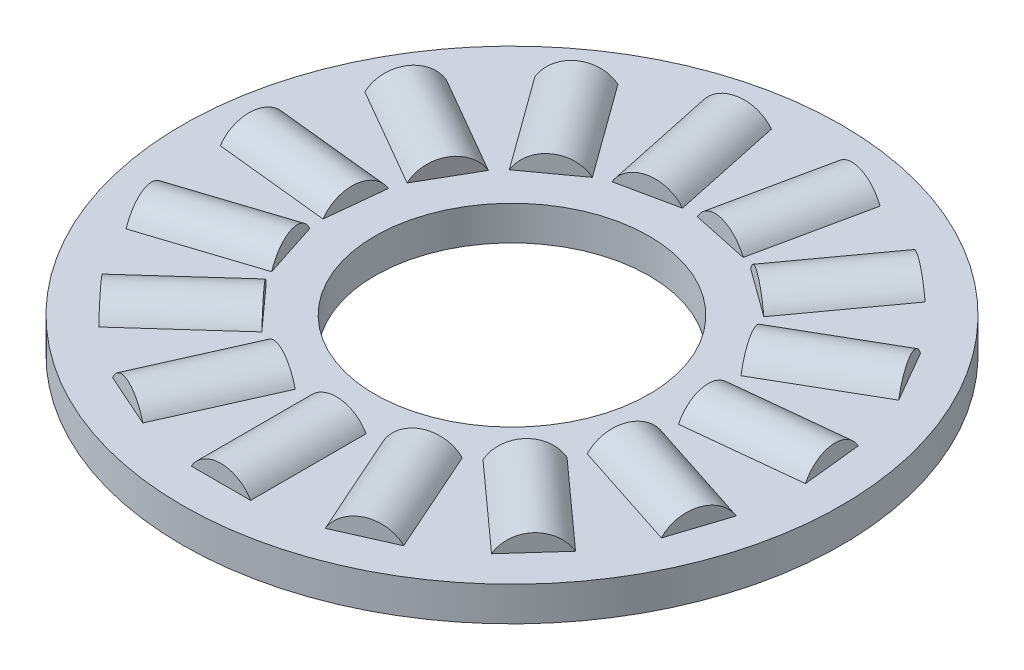
SolidWorks part; units mm, degrees
ref_plane "Front Plane" through (0, 0, 0) normal (0, 0, 1) x (1, 0, 0)
ref_plane "Top Plane" through (0, 0, 0) normal (0, 1, 0) x (1, 0, 0)
ref_plane "Right Plane" through (0, 0, 0) normal (1, 0, 0) x (0, 0, -1)
sketch "Sketch1" plane through (0, 0, 0) normal (1, 0, 0) x (0, 0, -1)
  line L0 (-9.525, 0) -> (9.525, 0) construction
  line L1 (0, -0.9922) -> (0, 0.9922) construction
  line L2 (-9.525, 0.4961) -> (-3.9624, 0.4961)
  line L3 (-9.525, 0.4961) -> (-9.525, -0.4961)
  line L4 (-9.525, -0.4961) -> (-3.9624, -0.4961)
  line L5 (-3.9624, 0.4961) -> (-3.9624, -0.4961)
  line L7 (-6.7437, 0.9922) -> (-6.7437, 0.4961) construction
  line L8 (-8.4125, 0.9922) -> (-5.0749, 0.9922) construction
  line L9 (-8.4125, 0.9922) -> (-8.4125, -0.9922) construction
  line L10 (-8.4125, -0.9922) -> (-5.0749, -0.9922) construction
  line L11 (-5.0749, 0.9922) -> (-5.0749, -0.9922) construction
  line L12 (9.525, 0.9922) -> (9.525, -0.9922) construction
  point P16 (-8.4125, 0)
  point P21 (9.525, 0)
  dimension "OD" = 19.05
  dimension "ID" = 7.9248
  dimension "Washer Thickness" = 0.9922
  dimension "D1" = 3.3376
  dimension "Thickness" = 1.9844
sketch "Sketch6" plane through (0, 0, 0) normal (0, 1, 0) x (1, 0, 0)
  circle A0 centre (0, 0) radius 9.525 construction
  circle A1 centre (0, 0) radius 3.9624 construction
  circle A2 centre (0, 0) radius 3.9688 construction
  dimension "For Shaft Diameter" = 7.9375
  dimension "OD" = 19.05
  dimension "ID" = 7.9248
sketch "Sketch5" plane through (0, 0, 0) normal (1, 0, 0) x (0, 0, -1)
  line L1 (-9.525, 0.4961) -> (-3.9624, 0.4961)
  line L2 (-9.525, 0.4961) -> (-9.525, -0.4961)
  line L3 (-9.525, -0.4961) -> (-3.9624, -0.4961)
  line L4 (-3.9624, 0.4961) -> (-3.9624, -0.4961)
revolve "Revolve3" add sketch "Sketch5" angle 360 about L1
sketch "Sketch3" plane through (0, 0, 0) normal (1, 0, 0) x (0, 0, -1)
  line L0 (-8.4125, 0.9922) -> (-8.4125, -0.9922) construction
  line L1 (-8.4125, 0) -> (-5.0749, 0)
  line L2 (-8.4125, 0) -> (-8.4125, 0.9922)
  line L3 (-8.4125, 0.9922) -> (-5.0749, 0.9922)
  line L4 (-5.0749, 0) -> (-5.0749, 0.9922)
revolve "Cut-Revolve1" cut sketch "Sketch3" angle 360 about L1
sketch "Sketch2" plane through (0, 0, 0) normal (1, 0, 0) x (0, 0, -1)
  line L1 (-8.4125, 0) -> (-5.0749, 0)
  line L2 (-8.4125, 0) -> (-8.4125, 0.9922)
  line L3 (-8.4125, 0.9922) -> (-5.0749, 0.9922)
  line L4 (-5.0749, 0) -> (-5.0749, 0.9922)
revolve "Revolve2" add sketch "Sketch2" angle 360 about L1
ref_axis "Axis1" through (0, 0.9922, 0) along (0, -1, 0)
pattern_circular "CirPattern1" count 15 every 24 about axis through (0, 0.9922, 0) along (0, -1, 0) of bodies 187 411
pattern_circular "CirPattern2" count 15 every 24 about axis through (0, 0.9922, 0) along (0, -1, 0) of "Cut-Revolve1"
equation "\"Washer Thickness@Sketch1\" = \"Thickness@Sketch1\" * .5"
equation "\"Rollers@CirPattern1\"= \"OD@Sketch1\" * 20"
equation "\"Angle@CirPattern1\" = 360/\"Rollers@CirPattern1\""
equation "\"D1@CirPattern2\" = \"Rollers@CirPattern1\""
equation "\"D2@CirPattern2\" = \"Angle@CirPattern1\""
equation "\"D1@Sketch1\"=((\"OD@Sketch1\"-\"ID@Sketch1\")/2)*.6"
